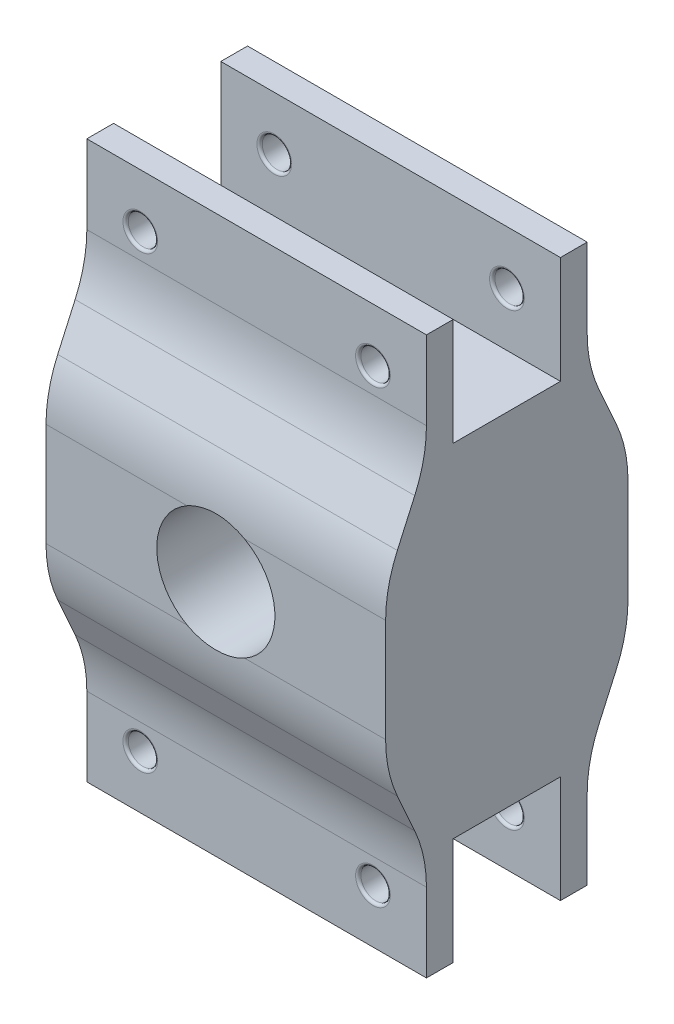
SolidWorks part; units mm, degrees
ref_plane "Front Plane" through (0, 0, 0) normal (0, 0, 1) x (1, 0, 0)
ref_plane "Top Plane" through (0, 0, 0) normal (0, 1, 0) x (1, 0, 0)
ref_plane "Right Plane" through (0, 0, 0) normal (1, 0, 0) x (0, 0, -1)
sketch "Sketch1" plane through (0, 0, 0) normal (1, 0, 0) x (0, 0, -1)
  line L0 (-15.025, 32.02) -> (-22.6575, 15)
  line L1 (0, 0) -> (50000, 0) construction
  line L3 (-10.025, 52.07) -> (-10.025, 32.02)
  line L6 (-10.025, 32.02) -> (10.025, 32.02)
  line L7 (-10.025, 52.07) -> (-15.025, 52.07)
  line L8 (-15.025, 52.07) -> (-15.025, 32.02)
  line L20 (-22.6575, 15) -> (-22.6575, -15)
  line L28 (0, 0) -> (0, 50000) construction
  line L29 (22.6575, 15) -> (22.6575, -15)
  line L30 (15.025, 52.07) -> (15.025, 32.02)
  line L31 (10.025, 52.07) -> (15.025, 52.07)
  line L32 (10.025, 52.07) -> (10.025, 32.02)
  line L33 (15.025, 32.02) -> (22.6575, 15)
  line L34 (15.025, -32.02) -> (22.6575, -15)
  line L35 (10.025, -52.07) -> (10.025, -32.02)
  line L36 (10.025, -52.07) -> (15.025, -52.07)
  line L37 (15.025, -52.07) -> (15.025, -32.02)
  line L38 (-15.025, -52.07) -> (-15.025, -32.02)
  line L39 (-10.025, -52.07) -> (-15.025, -52.07)
  line L40 (-10.025, -32.02) -> (10.025, -32.02)
  line L41 (-10.025, -52.07) -> (-10.025, -32.02)
  line L42 (-15.025, -32.02) -> (-22.6575, -15)
  point P17 (0, 32.02)
  point P22 (22.6575, 0)
  point P23 (-22.6575, 0)
  point P27 (0, -32.02)
  dimension "D5" = 20.05
  dimension "D6" = 52.07
  dimension "D1" = 10.025
  dimension "D2" = 15
  dimension "D3" = 5
extrude "Boss-Extrude1" add sketch "Sketch1" along normal mid plane 63.5
sketch "Sketch2" plane through (0, 0, 15.025) normal (0, 0, 1) x (1, 0, 0)
  line L1 (31.75, 52.07) -> (-31.75, 52.07) construction
  line L2 (-31.75, 52.07) -> (-31.75, 32.02) construction
  line L3 (0, 0) -> (0, 19.2106) construction
  circle A5 centre (-21.75, 42.07) radius 2.75
  circle A6 centre (21.75, 42.07) radius 2.75
  dimension "D2" = 10
  dimension "D1" = 5.5
  dimension "D3" = 10
extrude "Cut-Extrude1" cut sketch "Sketch2" against normal through all
mirror "Mirror1" about plane through (0, 0, 0) normal (0, 1, 0) of "Cut-Extrude1"
sketch "Sketch3" plane through (0, 0, 22.6575) normal (0, 0, 1) x (1, 0, 0)
  circle A0 centre (0, 0) radius 11.049
  dimension "D1" = 22.098
extrude "Cut-Extrude2" cut sketch "Sketch3" against normal through all
fillet "Fillet1" radius 0.5 15 edges at (-21.75, 44.82, -10.025) (24.5, 42.07, -15.025) (21.75, 44.82, -10.025) (21.75, 39.32, 10.025) (19, 42.07, 15.025) (-21.75, 39.32, 10.025) (-19, 42.07, 15.025) (21.75, -39.32, -10.025) (24.5, -42.07, -15.025) (-21.75, -39.32, -10.025) (-19, -42.07, -15.025) (21.75, -44.82, 10.025) (19, -42.07, 15.025) (-21.75, -44.82, 10.025) (-19, -42.07, 15.025)
fillet "Fillet2" radius 25 8 edges at (0, 32.02, -15.025) (0, 15, -22.6575) (0, -15, -22.6575) (0, -32.02, -15.025) (0, -32.02, 15.025) (0, -15, 22.6575) (0, 15, 22.6575) (0, 32.02, 15.025)
